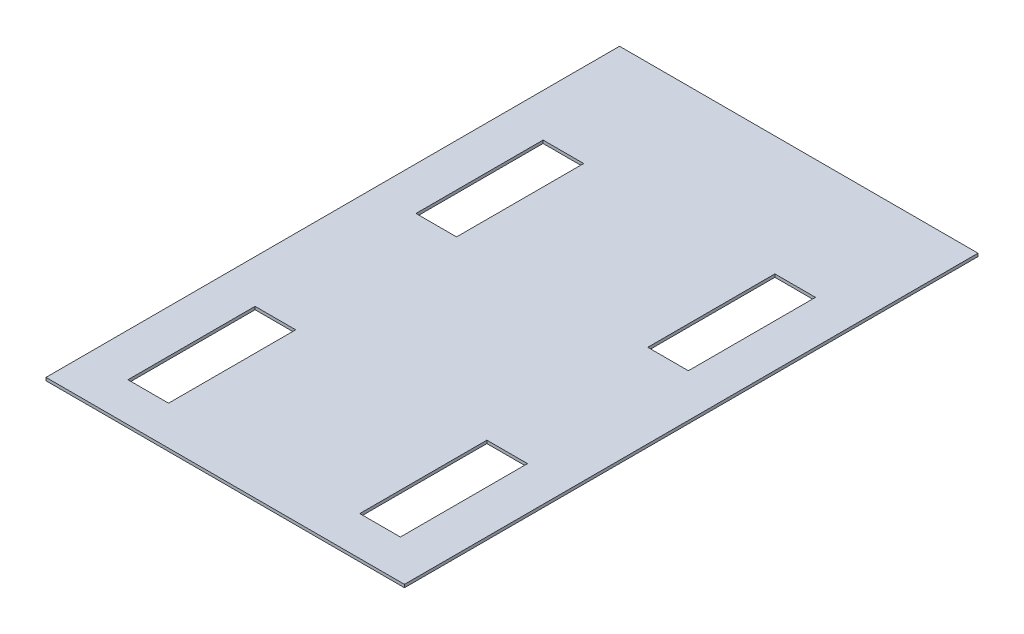
SolidWorks part; units mm, degrees
ref_plane "Front Plane" through (0, 0, 0) normal (0, 0, 1) x (1, 0, 0)
ref_plane "Top Plane" through (0, 0, 0) normal (0, 1, 0) x (1, 0, 0)
ref_plane "Right Plane" through (0, 0, 0) normal (1, 0, 0) x (0, 0, -1)
sketch "Sketch1" plane through (0, 0, 0) normal (0, 1, 0) x (1, 0, 0)
  line L1 (-190.5, -304.8) -> (190.5, -304.8)
  line L2 (-190.5, -304.8) -> (-190.5, 304.8)
  line L3 (-190.5, 304.8) -> (190.5, 304.8)
  line L4 (190.5, -304.8) -> (190.5, 304.8)
  line L5 (0, 304.8) -> (0, -304.8) construction
  line L6 (-190.5, 0) -> (190.5, 0) construction
  point P0 (0, 0)
  dimension "D1" = 381
  dimension "D2" = 609.6
extrude "Boss-Extrude1" add sketch "Sketch1" along normal blind 3.175
sketch "Sketch2" plane through (0, 3.175, 0) normal (0, 1, 0) x (1, 0, 0)
  line L0 (0, -1000) -> (0, 49000) construction
  line L5 (190.5, 304.8) -> (-190.5, 304.8) construction
  line L6 (101.6, -263.4234) -> (144.78, -263.4234)
  line L7 (101.6, 42.672) -> (144.78, 42.672)
  line L8 (101.6, 42.672) -> (101.6, 177.8)
  line L9 (101.6, 177.8) -> (144.78, 177.8)
  line L10 (144.78, 42.672) -> (144.78, 177.8)
  line L11 (123.19, 177.8) -> (123.19, 42.672) construction
  line L12 (101.6, 110.236) -> (144.78, 110.236) construction
  line L17 (101.6, -263.4234) -> (101.6, -128.2954)
  line L18 (101.6, -128.2954) -> (144.78, -128.2954)
  line L23 (144.78, -263.4234) -> (144.78, -128.2954)
  line L24 (123.19, -128.2954) -> (123.19, -263.4234) construction
  line L25 (101.6, -195.8594) -> (144.78, -195.8594) construction
  line L26 (-123.19, -128.2954) -> (-123.19, -263.4234) construction
  line L27 (-144.78, -263.4234) -> (-144.78, -128.2954)
  line L28 (-101.6, -263.4234) -> (-101.6, -128.2954)
  line L29 (-101.6, -263.4234) -> (-144.78, -263.4234)
  line L30 (-101.6, -195.8594) -> (-144.78, -195.8594) construction
  line L31 (-101.6, -128.2954) -> (-144.78, -128.2954)
  line L32 (-101.6, 110.236) -> (-144.78, 110.236) construction
  line L33 (-123.19, 177.8) -> (-123.19, 42.672) construction
  line L34 (-144.78, 42.672) -> (-144.78, 177.8)
  line L35 (-101.6, 177.8) -> (-144.78, 177.8)
  line L36 (-101.6, 42.672) -> (-101.6, 177.8)
  line L37 (-101.6, 42.672) -> (-144.78, 42.672)
  point P1 (123.19, -195.8594)
  point P4 (123.19, 110.236)
  point P20 (-123.19, -195.8594)
  point P29 (-123.19, 110.236)
  dimension "D1" = 135.128
  dimension "D2" = 43.18
  dimension "D3" = 135.128
  dimension "D4" = 306.0954
  dimension "D5" = 127
  dimension "D6" = 123.19
extrude "Cut-Extrude1" cut sketch "Sketch2" against normal through all
